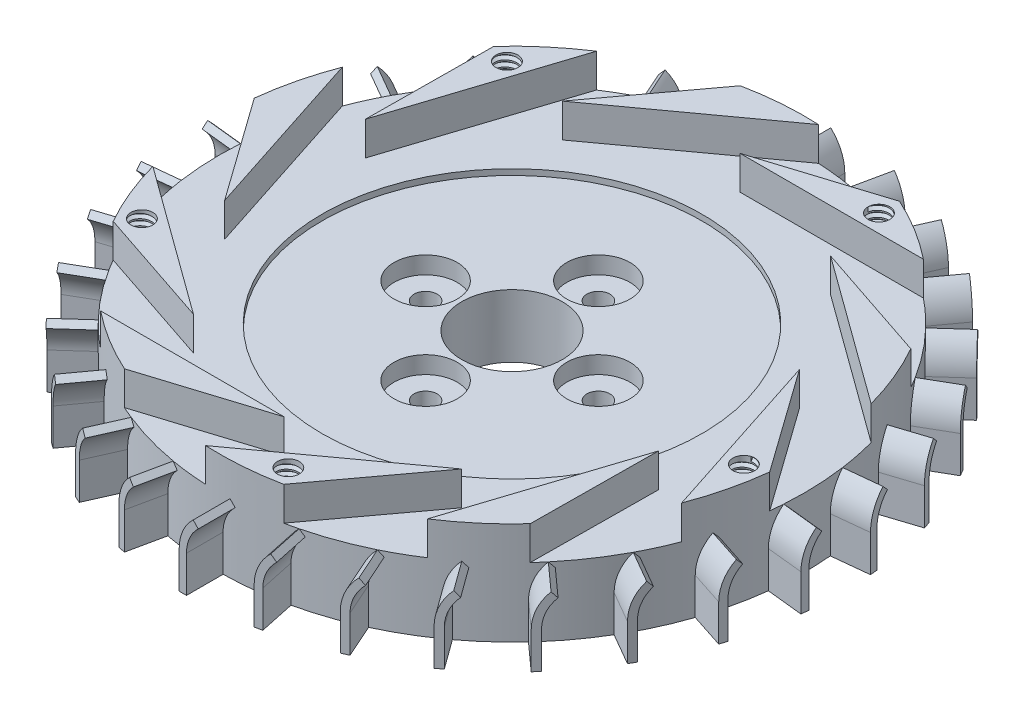
SolidWorks part; units mm, degrees
material "6061-T6 (SS)"
ref_plane "Front Plane" through (0, 0, 0) normal (0, 0, 1) x (1, 0, 0)
ref_plane "Top Plane" through (0, 0, 0) normal (0, 1, 0) x (1, 0, 0)
ref_plane "Right Plane" through (0, 0, 0) normal (1, 0, 0) x (0, 0, -1)
sketch "Sketch1" plane through (0, 0, 0) normal (1, 0, 0) x (0, 0, -1)
  line L0 (0, 26.2631) -> (0, -3.7705) construction
  line L1 (0, -3.7705) -> (-50.8, -3.7705)
  line L2 (-50.8, -3.7705) -> (-50.8, 8.1675)
  line L3 (-33.0001, 8.1675) -> (-50.8, 8.1675)
  line L4 (-33.0001, 8.1675) -> (-33.0001, 7.1515)
  line L5 (-33.0001, 7.1515) -> (0, 7.1515)
  line L6 (0, 7.1515) -> (0, -3.7705)
  dimension "D1" = 33.0001
  dimension "D2" = 50.8
  dimension "D3" = 1.016
  dimension "D4" = 11.938
revolve "Revolve1" add sketch "Sketch1" angle 360 about L0
sketch "Sketch2" plane through (0, 8.1675, 0) normal (0, 1, 0) x (1, 0, 0)
  line L8 (0, 39.6001) -> (19.9397, 39.6001) construction
  line L9 (0, 39.6001) -> (21.0453, 46.2356)
  line L10 (0, 39.6001) -> (31.8194, 39.6001)
  circle A0 centre (0, 0) radius 50.8 construction
  arc A1 (21.0453, 46.2356) -> (31.8194, 39.6001) centre (0, 0) cw
  circle A5 centre (0, 0) radius 33.0001 construction
  circle A7 centre (0, 0) radius 39.6001 construction
  point P9 (-2.4416, -40.4611)
  dimension "D1" = 66.0001
  dimension "D2" = 79.2001
  dimension "D3" = 17.5
extrude "Boss-Extrude1" add sketch "Sketch2" along normal blind 5.842
pattern_circular "CirPattern1" count 10 over 360 about axis through (0, 8.1675, 0) along (0, 1, 0) of "Boss-Extrude1"
ref_plane "Plane1" through (0, 0, 49.53) normal (0, 0, 1) x (1, 0, 0)
sketch "Sketch3" plane through (0, 0, 49.53) normal (0, 0, 1) x (1, 0, 0)
  line L0 (0, 0) -> (0, 9.7621) construction
  line L1 (0, -9.779) -> (0, 9.779) construction
  line L5 (10.1506, 8.1675) -> (23.2763, 8.1675) construction
  line L6 (-50.8, -3.7705) -> (50.8, -3.7705) construction
  line L7 (-0.635, 2.5795) -> (-0.635, -3.7705)
  line L10 (0.635, 2.5795) -> (0.635, -3.7705)
  line L11 (2.6678, 7.2361) -> (1.8044, 8.1675)
  line L12 (-0.635, -3.7705) -> (0.635, -3.7705)
  arc A4 (1.8044, 8.1675) -> (-0.635, 2.5795) centre (6.985, 2.5795) ccw
  arc A5 (2.6678, 7.2361) -> (0.635, 2.5795) centre (6.985, 2.5795) ccw
  arc A6 (2.6678, 7.2361) -> (0.635, 2.5795) centre (6.985, 2.5795) ccw construction
  point P20 (0, -3.7705)
  dimension "D1" = 1.27
  dimension "D2" = 6.35
  dimension "D3" = 6.35
extrude "Boss-Extrude2" add sketch "Sketch3" along normal blind 7.62 and the other way blind 0.254
pattern_circular "CirPattern16" count 30 over 360 about axis through (0, -3.7705, 0) along (0, 1, 0) of "Boss-Extrude2"
sketch "Sketch4" plane through (0, 7.1515, 0) normal (0, 1, 0) x (1, 0, 0)
  circle A0 centre (0, 0) radius 8.7312
  dimension "D1" = 17.4625
extrude "Cut-Extrude1" cut sketch "Sketch4" against normal up to next
sketch "Sketch5" plane through (0, -3.7705, 0) normal (0, -1, 0) x (-1, 0, 0)
  circle A0 centre (0, 0) radius 44.45
  dimension "D1" = 88.9
extrude "Cut-Extrude2" cut sketch "Sketch5" against normal blind 6.35
sketch "Sketch6" plane through (0, 2.5795, 0) normal (0, -1, 0) x (1, 0, 0)
  circle A0 centre (0, 0) radius 19.05
  circle A1 centre (0, 0) radius 8.7312 construction
  circle A2 centre (0, 0) radius 8.7312
  dimension "D1" = 38.1
extrude "Boss-Extrude3" add sketch "Sketch6" along normal up to surface (6.35 mm away) up to face at (0, -3.7705, -44.45)
sketch "Sketch9" plane through (0, 7.1515, 0) normal (0, 1, 0) x (1, 0, 0)
  circle A0 centre (0, 15) radius 2
  dimension "D1" = 4
  dimension "D2" = 15
extrude "Cut-Extrude3" cut sketch "Sketch9" against normal up to next
pattern_circular "CirPattern17" count 4 over 360 about axis through (0, 7.1515, 0) along (0, 1, 0) of "Cut-Extrude3"
ref_plane "Plane2" through (0, 0, 50.8) normal (0, 0, 1) x (1, 0, 0)
hole_wizard "#10-24 Tapped Hole2" positions "Sketch13" profile "Sketch14" tap size "#10-24" standard "ANSI Inch" end condition through all
sketch "Sketch13" plane through (0, 14.0095, 0) normal (0, 1, 0) x (1, 0, 0)
  point P0 (21.0453, 42.672)
  dimension "D1" = 42.672
  dimension "D2" = 0
sketch "Sketch14" plane through (21.0453, 14.0095, -42.672) normal (1, 0, 0) x (0, 0, 1)
  line L0 (0, 0) -> (0, 17.78)
  line L1 (0, 17.78) -> (1.8986, 17.78)
  line L2 (1.8986, 17.78) -> (1.8986, 0)
  line L5 (1.8986, 0) -> (0, 0)
  line L11 (0, -6.35) -> (0, 107.95) construction
  dimension "Thru Tap Drill Dia." = 3.7973
  dimension "Thru Tap Drill Depth" = 17.78
cosmetic thread "Hole Thread2" parameters "D2"=4.826
thread "Thread1" pitch 1.0583 method cut profile "Thread Profile1" start angle 0, offset 0, length 12.54, pitch 1.0583, diameter 3.7973
ref_plane "Plane3" through (19.1467, 14.0095, -42.672) normal (0, 0, 1) x (-1, 0, 0)
sketch "Thread Profile1" plane through (19.1467, 14.0095, -42.672) normal (0, 0, 1) x (-1, 0, 0)
  line L0 (0, 0) -> (0, 1.0583) construction
  line L1 (0, 0) -> (0.5728, 0.3307)
  line L2 (0.5728, 0.3307) -> (0.5728, 0.463)
  line L3 (0.5728, 0.463) -> (0, 0.7937)
  line L4 (0.5728, 0.3969) -> (0, 0.3969) construction
  line L11 (0, 0) -> (0, 0.7937)
  point P2 (0, 0)
  dimension "Pitch" = 1.0583
  dimension "Profile_Angle" = 60
  dimension "Profile_Land" = 0.1323
  dimension "Profile_Height" = 0.5728
pattern_circular "CirPattern19" count 5 over 360 about axis through (0, 7.1515, 0) along (0, 1, 0) of "#10-24 Tapped Hole2"
cosmetic thread "Hole Thread3" parameters "D2"=4.826
cosmetic thread "Hole Thread4" parameters "D2"=4.826
cosmetic thread "Hole Thread5" parameters "D2"=4.826
cosmetic thread "Hole Thread6" parameters "D2"=4.826
pattern_circular "CirPattern20" count 5 over 360 about axis through (0, 8.1675, 0) along (0, 1, 0) of "Thread1"
sketch "Sketch15" plane through (0, 7.1515, 0) normal (0, 1, 0) x (1, 0, 0)
  circle A0 centre (0, 15) radius 5.5
  circle A1 centre (15, 0) radius 5.5
  circle A2 centre (0, -15) radius 5.5
  circle A3 centre (-15, 0) radius 5.5
  dimension "D1" = 11
extrude "Cut-Extrude4" cut sketch "Sketch15" against normal blind 3
ref_plane "Plane4" through (46.4081, -3.7705, -20.6622) normal (0.9135, 0, -0.4067) x (-0.4067, 0, -0.9135)
sketch "Sketch16" plane through (46.4081, -3.7705, -20.6622) normal (0.9135, 0, -0.4067) x (-0.4067, 0, -0.9135)
  line L0 (-3.175, 0) -> (-3.175, 3.175)
  line L1 (3.175, 3.175) -> (3.175, 0)
  line L2 (3.175, 0) -> (-3.175, 0)
  line L3 (-4.6781, 0) -> (4.6781, 0) construction
  arc A0 (-3.175, 3.175) -> (3.175, 3.175) centre (0, 3.175) cw
  point P7 (0, 0)
  point P8 (0, 6.001)
  dimension "D2" = 3.175
  dimension "D1" = 3.175
extrude "Cut-Extrude5" cut sketch "Sketch16" against normal blind 7.366 and the other way blind 2.54
